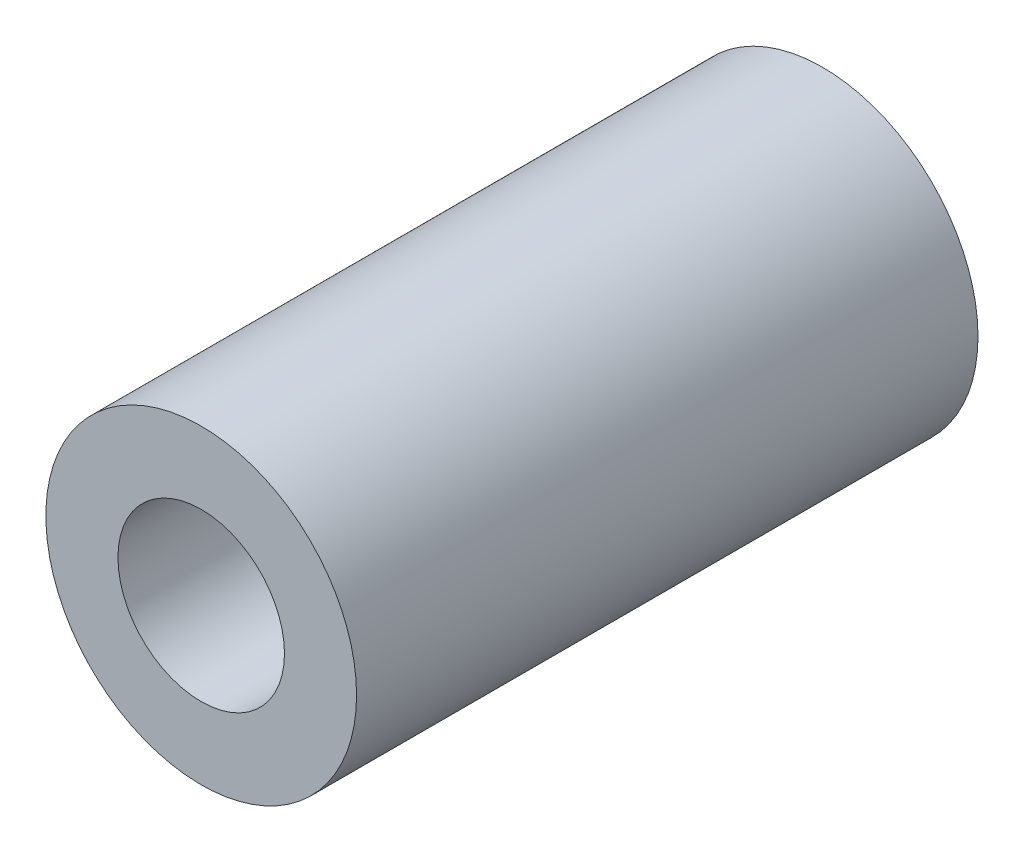
SolidWorks part; units mm, degrees
ref_plane "Front Plane" through (0, 0, 0) normal (0, 0, 1) x (1, 0, 0)
ref_plane "Top Plane" through (0, 0, 0) normal (0, 1, 0) x (1, 0, 0)
ref_plane "Right Plane" through (0, 0, 0) normal (1, 0, 0) x (0, 0, -1)
sketch "Sketch1" plane through (0, 0, 0) normal (0, 0, 1) x (1, 0, 0)
  circle A0 centre (0, 0) radius 4.7625
  circle A1 centre (0, 0) radius 2.5527
  dimension "D1" = 5.1054
  dimension "D2" = 9.525
extrude "Boss-Extrude1" add sketch "Sketch1" along normal mid plane 19.05 contours A0 A1 region at (-4.6278, 0, 0)
